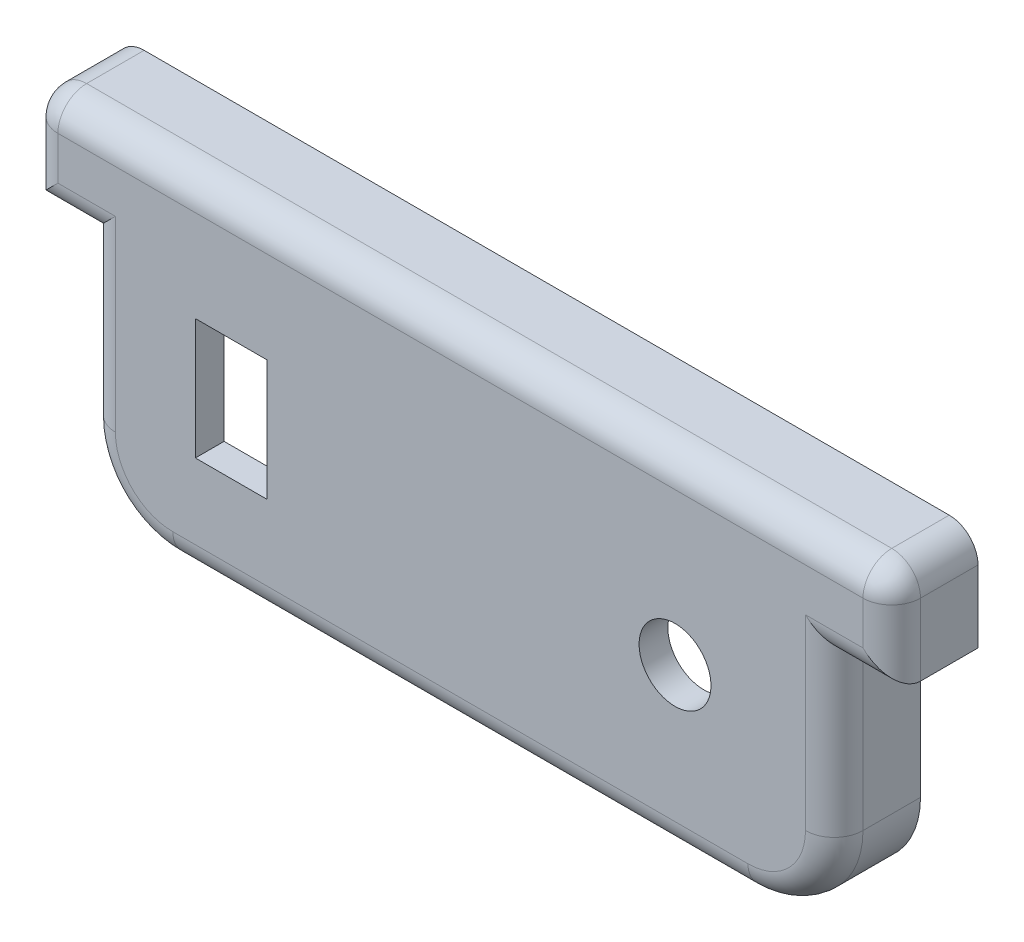
SolidWorks part; units mm, degrees
ref_plane "Front Plane" through (0, 0, 0) normal (0, 0, 1) x (1, 0, 0)
ref_plane "Top Plane" through (0, 0, 0) normal (0, 1, 0) x (1, 0, 0)
ref_plane "Right Plane" through (0, 0, 0) normal (1, 0, 0) x (0, 0, -1)
sketch "Sketch1" plane through (0, 0, 0) normal (0, 0, 1) x (1, 0, 0)
  line L3 (40, 52.5) -> (40, 80)
  line L4 (-70, 42.5) -> (30, 42.5)
  line L5 (-80, 80) -> (-80, 52.5)
  line L6 (-85, 80) -> (-85, 52.5)
  line L7 (-70, 37.5) -> (30, 37.5)
  line L8 (45, 52.5) -> (45, 80)
  line L9 (45, 80) -> (40, 80)
  line L10 (-85, 80) -> (-80, 80)
  arc A2 (30, 42.5) -> (40, 52.5) centre (30, 52.5) ccw
  arc A3 (-80, 52.5) -> (-70, 42.5) centre (-70, 52.5) ccw
  arc A4 (-85, 52.5) -> (-70, 37.5) centre (-70, 52.5) ccw
  arc A5 (30, 37.5) -> (45, 52.5) centre (30, 52.5) ccw
  dimension "D1" = 5
extrude "Boss-Extrude2" add sketch "Sketch1" along normal blind 10
sketch "Sketch2" plane through (0, 0, 10) normal (0, 0, 1) x (1, 0, 0)
  line L0 (45, 52.5) -> (45, 80) construction
  line L1 (-85, 80) -> (-85, 52.5) construction
  line L2 (-70, 37.5) -> (30, 37.5) construction
  line L3 (45, 52.5) -> (45, 80)
  line L4 (-85, 80) -> (-85, 52.5)
  line L5 (-70, 37.5) -> (30, 37.5)
  line L6 (45, 80) -> (-85, 80)
  arc A0 (30, 37.5) -> (45, 52.5) centre (30, 52.5) ccw construction
  arc A1 (-85, 52.5) -> (-70, 37.5) centre (-70, 52.5) ccw construction
  arc A2 (30, 37.5) -> (45, 52.5) centre (30, 52.5) ccw
  arc A3 (-85, 52.5) -> (-70, 37.5) centre (-70, 52.5) ccw
extrude "Boss-Extrude3" add sketch "Sketch2" along normal blind 5
fillet "Fillet1" radius 10 5 edges at (-77.0711, 45.4289, 10) (-20, 42.5, 10) (37.0711, 45.4289, 10)
sketch "Sketch3" plane through (0, 80, 0) normal (0, 1, 0) x (1, 0, 0)
  line L0 (-80, 0) -> (-85, 0) construction
  line L1 (55, -15) -> (-95, -15)
  line L2 (55, -15) -> (55, 0)
  line L3 (55, 0) -> (-95, 0)
  line L4 (-95, -15) -> (-95, 0)
  line L5 (55, -15) -> (-95, 0) construction
  line L6 (55, 0) -> (-95, -15) construction
  line L7 (-20, -7.5) -> (-20, -15) construction
  line L8 (45, -15) -> (-85, -15) construction
  point P0 (-20, -7.5)
  dimension "D1" = 150
extrude "Boss-Extrude4" add sketch "Sketch3" along normal blind 17.5 contours L3 L4 L1 L2
sketch "Sketch5" plane through (0, 0, 0) normal (0, 0, -1) x (-1, 0, 0)
  line L0 (-55, 80) -> (-45, 80) construction
  line L1 (-51, 80) -> (0, 80)
  line L2 (-51, 80) -> (-51, 94.2307)
  line L3 (-51, 94.2307) -> (0, 94.2307)
  line L4 (0, 80) -> (0, 94.2307)
  line L5 (20, 97.5) -> (20, 80) construction
  line L6 (-55, 97.5) -> (95, 97.5) construction
  line L7 (-40, 80) -> (80, 80) construction
  line L8 (-30, 80) -> (70, 80) construction
  line L9 (40, 80) -> (91, 80)
  line L10 (40, 80) -> (40, 94.2307)
  line L11 (40, 94.2307) -> (91, 94.2307)
  line L12 (91, 80) -> (91, 94.2307)
  dimension "D1" = 20
  dimension "D2" = 51
  dimension "D3" = 20
  dimension "D4" = 51
extrude "Cut-Extrude1" cut sketch "Sketch5" against normal blind 3
fillet "Fillet2" radius 5 12 edges at (-20, 37.5, 15) (-80.6066, 41.8934, 15) (-95, 88.75, 15) (-20, 97.5, 15) (55, 88.75, 15) (40.6066, 41.8934, 15) (-95, 97.5, 7.5) (55, 97.5, 7.5)
sketch "Sketch6" plane through (0, 0, 10) normal (0, 0, -1) x (-1, 0, 0)
  circle A0 centre (-17.3145, 66.1049) radius 6.25
  dimension "D1" = 12.5
extrude "Cut-Extrude2" cut sketch "Sketch6" against normal through all
sketch "Sketch7" plane through (0, 0, 10) normal (0, 0, -1) x (-1, 0, 0)
  line L1 (53.5957, 76.5633) -> (66.0957, 76.5633)
  line L2 (53.5957, 76.5633) -> (53.5957, 55.5633)
  line L3 (53.5957, 55.5633) -> (66.0957, 55.5633)
  line L4 (66.0957, 76.5633) -> (66.0957, 55.5633)
  line L5 (53.5957, 76.5633) -> (66.0957, 55.5633) construction
  line L6 (53.5957, 55.5633) -> (66.0957, 76.5633) construction
  point P0 (59.8457, 66.0633)
  dimension "D1" = 21
  dimension "D2" = 12.5
extrude "Cut-Extrude3" cut sketch "Sketch7" against normal through all
